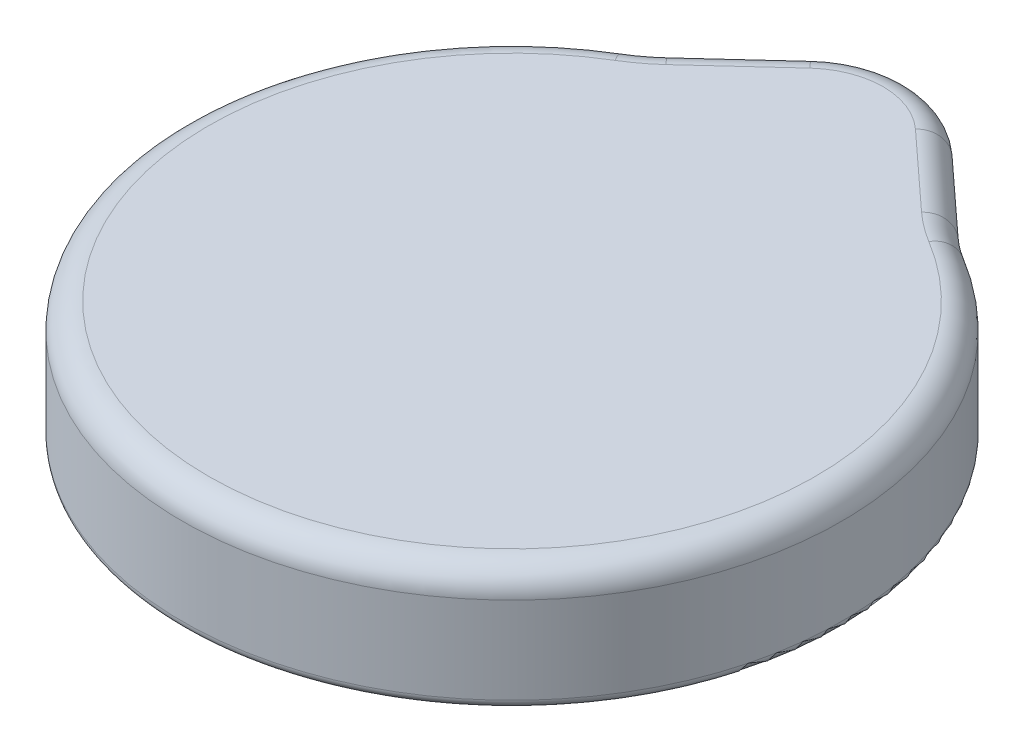
SolidWorks part; units mm, degrees
ref_plane "Front Plane" through (0, 0, 0) normal (0, 0, 1) x (1, 0, 0)
ref_plane "Top Plane" through (0, 0, 0) normal (0, 1, 0) x (1, 0, 0)
ref_plane "Right Plane" through (0, 0, 0) normal (1, 0, 0) x (0, 0, -1)
sketch "Sketch1" plane through (0, 0, 0) normal (0, 1, 0) x (1, 0, 0)
  line L0 (0, 0) -> (0, 47.3684) construction
  line L1 (0, 47.3684) -> (-17.0526, 31.705)
  line L2 (0, 47.3684) -> (17.0526, 31.705)
  line L3 (17.0526, 31.705) -> (-17.0526, 31.705) construction
  circle A0 centre (0, 0) radius 36
  point P3 (0, 31.705)
  dimension "D1" = 72
  dimension "D2" = 47.3684
  dimension "D3" = 34.1053
sketch "Sketch2" plane through (0, 0, 0) normal (0, 1, 0) x (1, 0, 0)
  line L0 (0, 47.3684) -> (-17.0526, 31.705) construction
  line L1 (0, 47.3684) -> (17.0526, 31.705) construction
  line L2 (-6.7647, 41.1548) -> (-15.4114, 33.2126)
  line L3 (6.7647, 41.1548) -> (15.4114, 33.2126)
  line L4 (8.1177, 42.6277) -> (16.7643, 34.6855)
  line L5 (-8.1177, 42.6277) -> (-16.7643, 34.6855)
  arc A0 (-6.7647, 41.1548) -> (6.7647, 41.1548) centre (0, 33.7901) cw
  circle A1 centre (0, 0) radius 36
  arc A2 (-18.6048, 30.8198) -> (18.6048, 30.8198) centre (0, 0) ccw
  arc A3 (18.6048, 30.8198) -> (15.4114, 33.2126) centre (28.9408, 47.942) cw
  arc A4 (-18.6048, 30.8198) -> (-15.4114, 33.2126) centre (-28.9408, 47.942) ccw
  arc A5 (-19.6384, 32.532) -> (19.6384, 32.532) centre (0, 0) ccw
  arc A6 (19.6384, 32.532) -> (16.7643, 34.6855) centre (28.9408, 47.942) cw
  arc A7 (-8.1177, 42.6277) -> (8.1177, 42.6277) centre (0, 33.7901) cw
  arc A8 (-19.6384, 32.532) -> (-16.7643, 34.6855) centre (-28.9408, 47.942) ccw
  dimension "D2" = 10
  dimension "D3" = 20
  dimension "D1" = 0
  dimension "D4" = 2
extrude "Boss-Extrude1" add sketch "Sketch2" against normal blind 10
extrude "Boss-Extrude2" add sketch "Sketch2<2>" along normal blind 4 contours A5 A6 L4 A7 L5 A8
sketch "Sketch2<2>" plane through (0, 0, 0) normal (0, 1, 0) x (1, 0, 0) same geometry as "Sketch2"
fillet "Fillet1" radius 1 6 edges at (-16.9483, 0, -31.9364) (-11.088, 0, -37.1837) (0, 0, -43.7901) (11.088, 0, -37.1837) (16.9483, 0, -31.9364) (0, 0, 36)
fillet "Fillet2" radius 3 6 edges at (-18.1475, 4, -33.5369) (-12.441, 4, -38.6566) (0, 4, -45.7901) (12.441, 4, -38.6566) (18.1475, 4, -33.5369) (0, 4, 38)
fillet "Fillet3" radius 1 12 edges at (-16.9483, -10, -31.9364) (-11.088, -10, -37.1837) (0, -10, -43.7901) (11.088, -10, -37.1837) (16.9483, -10, -31.9364) (-18.1475, -10, -33.5369) (-12.441, -10, -38.6566) (0, -10, -45.7901) (12.441, -10, -38.6566) (18.1475, -10, -33.5369) (0, -10, 36) (0, -10, 38)
equation "\"D2@Sketch1\"=125/190*\"D1@Sketch1\""
equation "\"D3@Sketch1\"=90/190*\"D1@Sketch1\""
